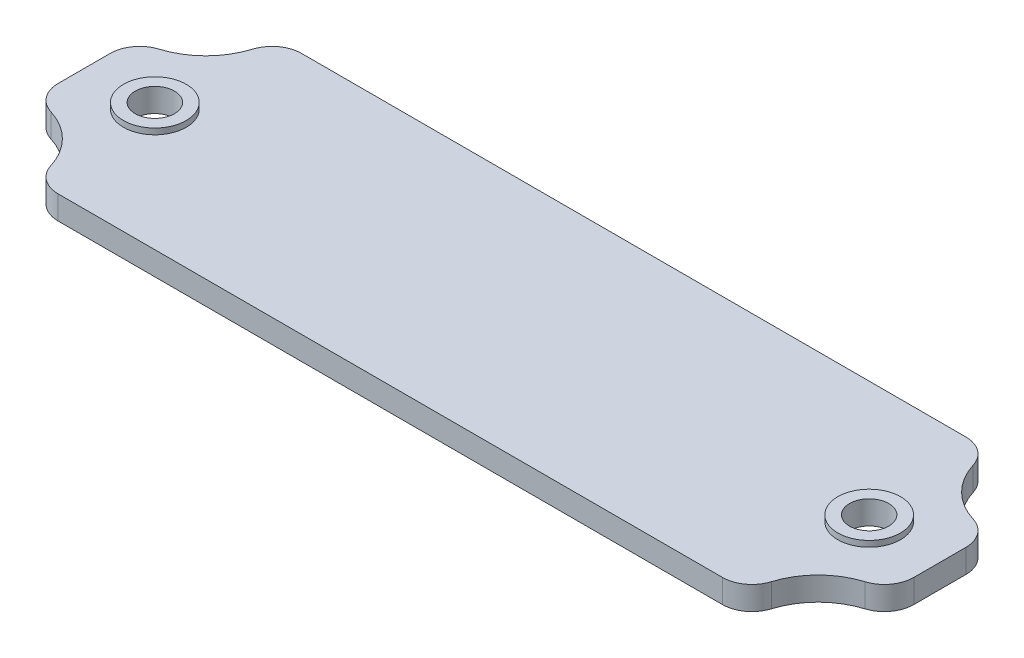
SolidWorks part; units mm, degrees
material "Brass"
ref_plane "Front Plane" through (0, 0, 0) normal (0, 0, 1) x (1, 0, 0)
ref_plane "Top Plane" through (0, 0, 0) normal (0, 1, 0) x (1, 0, 0)
ref_plane "Right Plane" through (0, 0, 0) normal (1, 0, 0) x (0, 0, -1)
sketch "Sketch2" plane through (0, 0, 0) normal (0, 1, 0) x (1, 0, 0)
  line L0 (0, -33.963) -> (0, 33.963) construction
  line L1 (-42.3139, -15.5) -> (42.3139, -15.5)
  line L2 (-54.5, -3.3139) -> (-54.5, 3.3139)
  line L3 (-42.3139, 15.5) -> (42.3139, 15.5)
  line L4 (54.5, -3.3139) -> (54.5, 3.3139)
  line L5 (-65.032, 0) -> (65.032, 0) construction
  arc A0 (-45.8981, 12.8529) -> (-51.8529, 6.8981) centre (-54.5, 15.5) cw
  arc A1 (-51.8529, -6.8981) -> (-45.8981, -12.8529) centre (-54.5, -15.5) cw
  arc A2 (45.8981, 12.8529) -> (51.8529, 6.8981) centre (54.5, 15.5) ccw
  arc A3 (45.8981, -12.8529) -> (51.8529, -6.8981) centre (54.5, -15.5) cw
  arc A4 (45.8981, 12.8529) -> (42.3139, 15.5) centre (42.3139, 11.75) ccw
  arc A5 (51.8529, 6.8981) -> (54.5, 3.3139) centre (50.75, 3.3139) cw
  arc A6 (51.8529, -6.8981) -> (54.5, -3.3139) centre (50.75, -3.3139) ccw
  arc A7 (45.8981, -12.8529) -> (42.3139, -15.5) centre (42.3139, -11.75) cw
  arc A8 (-45.8981, -12.8529) -> (-42.3139, -15.5) centre (-42.3139, -11.75) ccw
  arc A9 (-51.8529, -6.8981) -> (-54.5, -3.3139) centre (-50.75, -3.3139) cw
  arc A10 (-51.8529, 6.8981) -> (-54.5, 3.3139) centre (-50.75, 3.3139) ccw
  arc A11 (-45.8981, 12.8529) -> (-42.3139, 15.5) centre (-42.3139, 11.75) cw
  circle A12 centre (-45.5, 0) radius 2.5
  circle A13 centre (45.5, 0) radius 2.5
  point P0 (0, 0)
  point P3 (0, 15.5)
  point P11 (0, 0)
  point P12 (54.5, 0)
  point P20 (0, 0)
  point P29 (45.5, 15.5)
  point P32 (54.5, 6.5)
  point P35 (54.5, -6.5)
  point P38 (45.5, -15.5)
  point P41 (-45.5, -15.5)
  point P44 (-54.5, -6.5)
  point P47 (-54.5, 6.5)
  point P50 (-45.5, 15.5)
  dimension "D3" = 9
  dimension "D4" = 3.75
  dimension "D5" = 5
  dimension "D1" = 109
  dimension "D2" = 31
  dimension "D6" = 9
  dimension "D7" = 9
extrude "Boss-Extrude1" add sketch "Sketch2" along normal mid plane 1.5
sketch "Sketch3" plane through (0, 0.75, 0) normal (0, -1, 0) x (1, 0, 0)
  line L8 (53, -3.3139) -> (53, 3.3139)
  line L9 (42.3139, 14) -> (-42.3139, 14)
  line L10 (-53, 3.3139) -> (-53, -3.3139)
  line L11 (-42.3139, -14) -> (42.3139, -14)
  line L12 (53, -3.3139) -> (53, 3.3139)
  line L13 (42.3139, 14) -> (-42.3139, 14)
  line L14 (-53, 3.3139) -> (-53, -3.3139)
  line L15 (-42.3139, -14) -> (42.3139, -14)
  line L16 (54.5, -3.3139) -> (54.5, 3.3139)
  line L17 (42.3139, 15.5) -> (-42.3139, 15.5)
  line L18 (-54.5, 3.3139) -> (-54.5, -3.3139)
  line L19 (-42.3139, -15.5) -> (42.3139, -15.5)
  line L20 (54.5, -3.3139) -> (54.5, 3.3139)
  line L21 (42.3139, 15.5) -> (-42.3139, 15.5)
  line L22 (-54.5, 3.3139) -> (-54.5, -3.3139)
  line L23 (-42.3139, -15.5) -> (42.3139, -15.5)
  arc A24 (42.3139, -14) -> (44.4644, -12.4118) centre (42.3139, -11.75) ccw
  arc A25 (51.4118, -5.4644) -> (44.4644, -12.4118) centre (54.5, -15.5) ccw
  arc A26 (51.4118, -5.4644) -> (53, -3.3139) centre (50.75, -3.3139) ccw
  arc A27 (53, 3.3139) -> (51.4118, 5.4644) centre (50.75, 3.3139) ccw
  arc A28 (44.4644, 12.4118) -> (51.4118, 5.4644) centre (54.5, 15.5) ccw
  arc A29 (44.4644, 12.4118) -> (42.3139, 14) centre (42.3139, 11.75) ccw
  arc A30 (-42.3139, 14) -> (-44.4644, 12.4118) centre (-42.3139, 11.75) ccw
  arc A31 (-51.4118, 5.4644) -> (-44.4644, 12.4118) centre (-54.5, 15.5) ccw
  arc A32 (-51.4118, 5.4644) -> (-53, 3.3139) centre (-50.75, 3.3139) ccw
  arc A33 (-53, -3.3139) -> (-51.4118, -5.4644) centre (-50.75, -3.3139) ccw
  arc A34 (-44.4644, -12.4118) -> (-51.4118, -5.4644) centre (-54.5, -15.5) ccw
  arc A35 (-44.4644, -12.4118) -> (-42.3139, -14) centre (-42.3139, -11.75) ccw
  arc A36 (42.3139, -14) -> (44.4644, -12.4118) centre (42.3139, -11.75) ccw
  arc A37 (51.4118, -5.4644) -> (44.4644, -12.4118) centre (54.5, -15.5) ccw
  arc A38 (51.4118, -5.4644) -> (53, -3.3139) centre (50.75, -3.3139) ccw
  arc A39 (53, 3.3139) -> (51.4118, 5.4644) centre (50.75, 3.3139) ccw
  arc A40 (44.4644, 12.4118) -> (51.4118, 5.4644) centre (54.5, 15.5) ccw
  arc A41 (44.4644, 12.4118) -> (42.3139, 14) centre (42.3139, 11.75) ccw
  arc A42 (-42.3139, 14) -> (-44.4644, 12.4118) centre (-42.3139, 11.75) ccw
  arc A43 (-51.4118, 5.4644) -> (-44.4644, 12.4118) centre (-54.5, 15.5) ccw
  arc A44 (-51.4118, 5.4644) -> (-53, 3.3139) centre (-50.75, 3.3139) ccw
  arc A45 (-53, -3.3139) -> (-51.4118, -5.4644) centre (-50.75, -3.3139) ccw
  arc A46 (-44.4644, -12.4118) -> (-51.4118, -5.4644) centre (-54.5, -15.5) ccw
  arc A47 (-44.4644, -12.4118) -> (-42.3139, -14) centre (-42.3139, -11.75) ccw
  arc A48 (42.3139, -15.5) -> (45.8981, -12.8529) centre (42.3139, -11.75) ccw
  arc A49 (51.8529, -6.8981) -> (45.8981, -12.8529) centre (54.5, -15.5) ccw
  arc A50 (51.8529, -6.8981) -> (54.5, -3.3139) centre (50.75, -3.3139) ccw
  arc A51 (54.5, 3.3139) -> (51.8529, 6.8981) centre (50.75, 3.3139) ccw
  arc A52 (45.8981, 12.8529) -> (51.8529, 6.8981) centre (54.5, 15.5) ccw
  arc A53 (45.8981, 12.8529) -> (42.3139, 15.5) centre (42.3139, 11.75) ccw
  arc A54 (-42.3139, 15.5) -> (-45.8981, 12.8529) centre (-42.3139, 11.75) ccw
  arc A55 (-51.8529, 6.8981) -> (-45.8981, 12.8529) centre (-54.5, 15.5) ccw
  arc A56 (-51.8529, 6.8981) -> (-54.5, 3.3139) centre (-50.75, 3.3139) ccw
  arc A57 (-54.5, -3.3139) -> (-51.8529, -6.8981) centre (-50.75, -3.3139) ccw
  arc A58 (-45.8981, -12.8529) -> (-51.8529, -6.8981) centre (-54.5, -15.5) ccw
  arc A59 (-45.8981, -12.8529) -> (-42.3139, -15.5) centre (-42.3139, -11.75) ccw
  arc A60 (42.3139, -15.5) -> (45.8981, -12.8529) centre (42.3139, -11.75) ccw
  arc A61 (51.8529, -6.8981) -> (45.8981, -12.8529) centre (54.5, -15.5) ccw
  arc A62 (51.8529, -6.8981) -> (54.5, -3.3139) centre (50.75, -3.3139) ccw
  arc A63 (54.5, 3.3139) -> (51.8529, 6.8981) centre (50.75, 3.3139) ccw
  arc A64 (45.8981, 12.8529) -> (51.8529, 6.8981) centre (54.5, 15.5) ccw
  arc A65 (45.8981, 12.8529) -> (42.3139, 15.5) centre (42.3139, 11.75) ccw
  arc A66 (-42.3139, 15.5) -> (-45.8981, 12.8529) centre (-42.3139, 11.75) ccw
  arc A67 (-51.8529, 6.8981) -> (-45.8981, 12.8529) centre (-54.5, 15.5) ccw
  arc A68 (-51.8529, 6.8981) -> (-54.5, 3.3139) centre (-50.75, 3.3139) ccw
  arc A69 (-54.5, -3.3139) -> (-51.8529, -6.8981) centre (-50.75, -3.3139) ccw
  arc A70 (-45.8981, -12.8529) -> (-51.8529, -6.8981) centre (-54.5, -15.5) ccw
  arc A71 (-45.8981, -12.8529) -> (-42.3139, -15.5) centre (-42.3139, -11.75) ccw
  dimension "D1" = 1.5
extrude "Boss-Extrude2" add sketch "Sketch3" along normal blind 3
sketch "Sketch4" plane through (0, 0, 0) normal (0, 1, 0) x (1, 0, 0)
  circle A0 centre (-45.5, 0) radius 4
  circle A1 centre (45.5, 0) radius 4
  circle A2 centre (45.5, 0) radius 2.5 construction
  circle A3 centre (-45.5, 0) radius 2.5 construction
  circle A4 centre (45.5, 0) radius 2.5
  circle A5 centre (-45.5, 0) radius 2.5
  dimension "D1" = 8
extrude "Boss-Extrude3" add sketch "Sketch4" along normal mid plane 3
equation "\"A\" = 1.5"
equation "\"B\"= 109"
equation "\"D1@Sketch2\"=\"B\""
equation "\"D1@Boss-Extrude1\"=\"A\""
equation "\"D1@Sketch3\"=\"A\""
equation "\"D1@Boss-Extrude2\"=\"A\" * 2"
equation "\"D1@Sketch4\"=5+(\"A\" * 2)"
equation "\"D1@Boss-Extrude3\"=2 * \"A\""
